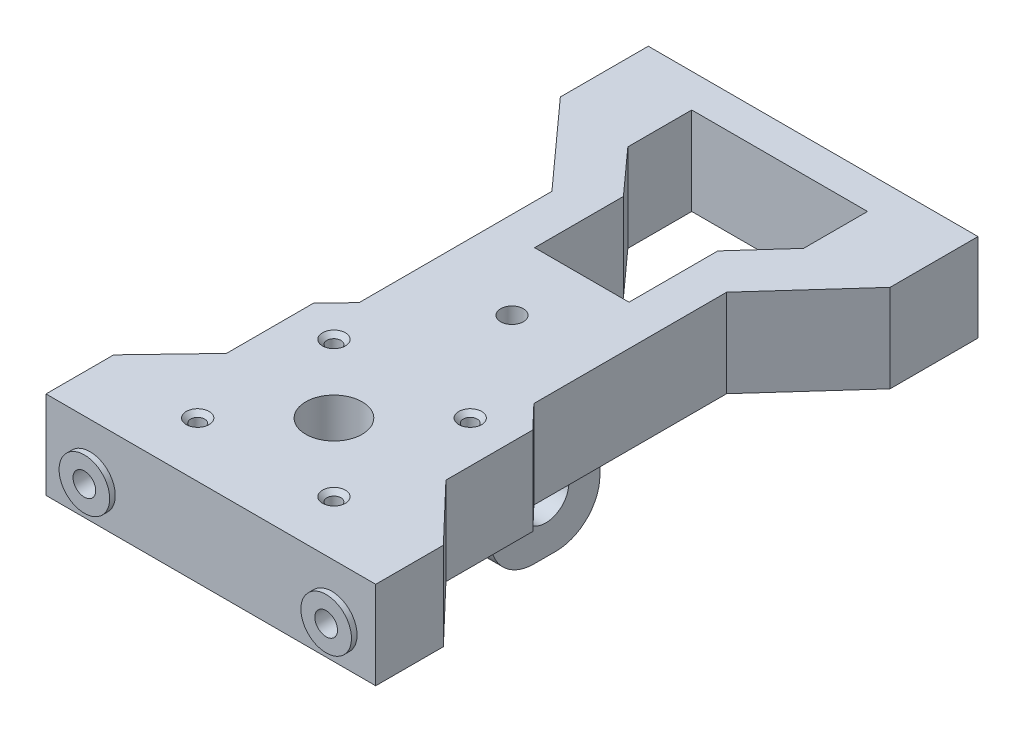
SolidWorks part; units mm, degrees
ref_plane "Front Plane" through (0, 0, 0) normal (0, 0, 1) x (1, 0, 0)
ref_plane "Top Plane" through (0, 0, 0) normal (0, 1, 0) x (1, 0, 0)
ref_plane "Right Plane" through (0, 0, 0) normal (1, 0, 0) x (0, 0, -1)
sketch "Sketch1" plane through (0, 0, 0) normal (1, 0, 0) x (0, 0, -1)
  line L0 (0, 0) -> (-68.5, 0)
  line L1 (0, 0) -> (0, 20)
  line L2 (-68.5, 0) -> (-68.5, 20)
  line L3 (0, 20) -> (-68.5, 20)
  dimension "D1" = 68.5
  dimension "D2" = 20
extrude "Boss-Extrude1" add sketch "Sketch1" along normal blind 75
mirror "Mirror1" about plane through (75, 0, 68.5) normal (0, 0, -1) of "Boss-Extrude1"
sketch "Sketch5" plane through (0, 0, 0) normal (0, -1, 0) x (1, 0, 0)
  line L0 (0, 68.5) -> (75, 68.5) construction
  line L1 (30, 56) -> (45, 56)
  line L2 (30, 56) -> (30, 81)
  line L3 (30, 81) -> (45, 81)
  line L4 (45, 56) -> (45, 81)
  line L5 (0, 137) -> (0, 0) construction
  line L6 (75, 137) -> (75, 0) construction
  line L7 (37.5, 0) -> (37.5, 137) construction
  line L8 (75, 0) -> (0, 0) construction
  line L9 (75, 137) -> (0, 137) construction
  point P10 (30, 68.5)
  point P17 (37.5, 56)
  dimension "D1" = 15
  dimension "D2" = 25
extrude "Boss-Extrude2" add sketch "Sketch5" along normal blind 24
sketch "Sketch6" plane through (30, 0, 0) normal (-1, 0, 0) x (0, 0, 1)
  line L0 (81, 0) -> (56, 0) construction
  line L9 (56, -12) -> (81, -12) construction
  line L10 (56, -24) -> (56, 0) construction
  line L11 (81, -24) -> (81, 0) construction
  circle A0 centre (68.3158, -12) radius 5.25
  dimension "D1" = 10.5
  dimension "D2" = 12
extrude "Cut-Extrude4" cut sketch "Sketch6" against normal through all
sketch "Sketch2" plane through (0, 0, 0) normal (0, -1, 0) x (1, 0, 0)
  line L0 (15.5, 131) -> (59.5, 131)
  line L1 (15.5, 131) -> (15.5, 87)
  line L2 (59.5, 131) -> (59.5, 87)
  line L3 (15.5, 87) -> (59.5, 87)
  line L4 (75, 137) -> (0, 137) construction
  line L5 (37.5, 137) -> (37.5, 81) construction
  line L6 (45, 81) -> (30, 81) construction
  point P5 (37.5, 137)
  point P6 (37.5, 131)
  point P12 (15.5, 109)
  point P13 (37.5, 109)
  dimension "D1" = 44
extrude "Cut-Extrude1" cut sketch "Sketch2" against normal blind 7
sketch "Sketch3" plane through (0, 7, 0) normal (0, -1, 0) x (1, 0, 0)
  line L0 (15.5, 109) -> (59.5, 109) construction
  line L1 (15.5, 131) -> (15.5, 87) construction
  line L2 (59.5, 87) -> (59.5, 131) construction
  line L4 (53, 124.5) -> (22, 124.5) construction
  line L5 (53, 124.5) -> (53, 93.5) construction
  line L6 (53, 93.5) -> (22, 93.5) construction
  line L7 (22, 124.5) -> (22, 93.5) construction
  line L8 (53, 124.5) -> (22, 93.5) construction
  line L9 (53, 93.5) -> (22, 124.5) construction
  circle A1 centre (37.5, 109) radius 6.4135
  circle A2 centre (22, 93.5) radius 1.6
  circle A3 centre (22, 124.5) radius 1.6
  circle A4 centre (53, 124.5) radius 1.6
  circle A5 centre (53, 93.5) radius 1.6
  point P8 (37.5, 109)
  dimension "D2" = 12.827
  dimension "D5" = 3.2
  dimension "D3" = 31
  dimension "D4" = 31
extrude "Cut-Extrude2" cut sketch "Sketch3" against normal through all
sketch "Sketch4" plane through (0, 7, 0) normal (0, -1, 0) x (1, 0, 0)
  circle A0 centre (37.5, 109) radius 12.5
  dimension "D1" = 25
extrude "Cut-Extrude3" cut sketch "Sketch4" against normal blind 3
chamfer "Chamfer1" distance 1 angle 45 4 edges at (22, 20, 122.9) (53, 20, 122.9) (53, 20, 91.9) (22, 20, 91.9)
fillet "Fillet1" radius 10 2 edges at (37.5, -24, 56) (37.5, -24, 81)
fillet "Fillet2" radius 5 1 edges at (30, 0, 68.5)
sketch "Sketch7" plane through (0, 0, 0) normal (0, 0, -1) x (-1, 0, 0)
  line L0 (-75, 0) -> (0, 0) construction
  line L1 (0, 0) -> (0, 20) construction
  circle A0 centre (-10, 7.874) radius 2.5797
  circle A1 centre (-10, 7.874) radius 5.7547
  dimension "D1" = 5.1594
  dimension "D4" = 3.175
  dimension "D2" = 7.874
  dimension "D3" = 10
ref_plane "Plane1" through (37.5, 0, 0) normal (-1, 0, 0) x (0, 0, 1)
ref_plane "Plane2" through (0, 0, 68.5) normal (0, 0, 1) x (1, 0, 0)
sketch "Sketch16" plane through (0, 20, 0) normal (0, 1, 0) x (1, 0, 0)
  line L0 (0, -68.5) -> (75, -68.5) construction
  line L1 (0, 0) -> (0, -137) construction
  line L2 (75, 0) -> (75, -137) construction
  circle A0 centre (37.5, -68.5) radius 2.5797
  point P9 (37.5, -68.5)
  dimension "D1" = 5.1594
extrude "Cut-Extrude6" cut sketch "Sketch16" against normal blind 20 contours A0
extrude "Cut-Extrude7" cut sketch "Sketch7" against normal blind 12.7 contours A0 region at (10, 7.874, 0)
extrude "Boss-Extrude3" add sketch "Sketch7<3>" along normal blind 1.27
sketch "Sketch7<3>" plane through (0, 0, 0) normal (0, 0, -1) x (-1, 0, 0) same geometry as "Sketch7"
mirror "Mirror2" about plane through (37.5, 0, 0) normal (-1, 0, 0) of "Boss-Extrude3", "Cut-Extrude7"
mirror "Mirror3" about plane through (0, 0, 68.5) normal (0, 0, 1) of "Boss-Extrude3", "Cut-Extrude7", "Mirror2"
sketch "Sketch18" plane through (0, 20, 0) normal (0, 1, 0) x (1, 0, 0)
  line L0 (62.4588, -88.7206) -> (57.3739, -83.4002)
  line L2 (48.2374, -32.4211) -> (48.2374, -52.62)
  line L5 (75, 0) -> (75, -137) construction
  line L6 (57.3739, -83.4002) -> (57.3739, -39.5494)
  line L7 (57.3739, -39.5494) -> (75, -20)
  line L8 (48.2374, -32.4211) -> (57.4934, -22.1551)
  line L9 (57.4934, -22.1551) -> (57.4934, -7.62)
  line L10 (57.4934, -7.62) -> (37.4934, -7.62)
  line L11 (37.4934, -52.62) -> (37.4934, -7.62)
  line L12 (48.2374, -52.62) -> (37.4934, -52.62)
  line L15 (57.3739, -49.7294) -> (48.2374, -49.7294) construction
  line L16 (63.0492, -33.2548) -> (54.4644, -25.5146) construction
  line L17 (75, 0) -> (0, 0) construction
  line L18 (62.4588, -88.7206) -> (62.4588, -108.491)
  line L19 (62.4588, -108.491) -> (75, -121.613)
  line L20 (75, -121.613) -> (75, -20)
  dimension "D1" = 7.62
  dimension "D2" = 45
  dimension "D3" = 20
  dimension "D4" = 20
extrude "Cut-Extrude8" cut sketch "Sketch18" against normal through all
mirror "Mirror4" about plane through (37.5, 0, 0) normal (-1, 0, 0) of "Cut-Extrude8"
